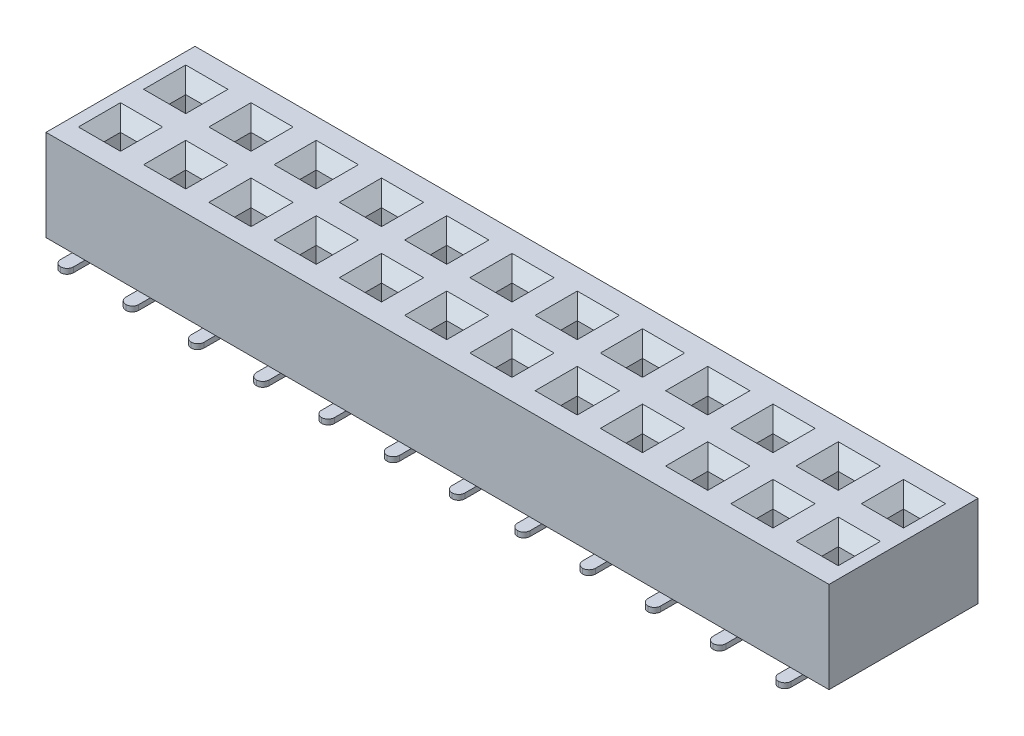
SolidWorks part; units mm, degrees
ref_plane "Ebene vorne" through (0, 0, 0) normal (0, 0, 1) x (1, 0, 0)
ref_plane "Ebene oben" through (0, 0, 0) normal (0, 1, 0) x (1, 0, 0)
ref_plane "Ebene rechts" through (0, 0, 0) normal (1, 0, 0) x (0, 0, -1)
sketch "Sketch1" plane through (0, 0, 0) normal (0, 1, 0) x (1, 0, 0)
  line L0 (0, 0) -> (20.1529, 0) construction
  line L1 (0, 2.9) -> (30.48, 2.9)
  line L2 (0, 2.9) -> (0, -2.9)
  line L3 (0, -2.9) -> (30.48, -2.9)
  line L4 (30.48, 2.9) -> (30.48, -2.9)
  dimension "D1" = 5.8
  dimension "D2" = 30.48
extrude "Boss-Extrude1" add sketch "Sketch1" along normal blind 3.55
sketch "Sketch2" plane through (0, 3.55, 0) normal (0, 1, 0) x (1, 0, 0)
  line L0 (0, 1.27) -> (30.48, 1.27) construction
  line L1 (0, 2.9) -> (0, -2.9) construction
  line L2 (30.48, -2.9) -> (30.48, 2.9) construction
  line L4 (0.95, 1.59) -> (1.59, 1.59)
  line L5 (0.95, 1.59) -> (0.95, 0.95)
  line L6 (0.95, 0.95) -> (1.59, 0.95)
  line L7 (1.59, 1.59) -> (1.59, 0.95)
  point P11 (1.27, 1.59)
  dimension "D1" = 0.64
  dimension "D2" = 1.27
  dimension "D3" = 1.27
extrude "Cut-Extrude1" cut sketch "Sketch2" against normal through all
chamfer "Chamfer1" distance 0.5 angle 45 4 edges at (1.27, 3.55, -0.95) (0.95, 3.55, -1.27) (1.27, 3.55, -1.59) (1.59, 3.55, -1.27)
pattern_linear "LPattern1" count 12 spacing 2.54 along (1, 0, 0) count 2 spacing 2.54 along (0, 0, 1) of "Cut-Extrude1", "Chamfer1"
sketch "Sketch3" plane through (0, 0, 0) normal (0, -1, 0) x (1, 0, 0)
  line L0 (1.27, 1.59) -> (1.27, -4.8164) construction
  line L1 (0.95, 1.59) -> (1.59, 1.59) construction
  line L2 (0, 0) -> (5.3011, 0) construction
  line L3 (1.02, 1.59) -> (1.52, 1.59)
  line L4 (1.02, 1.59) -> (1.02, 3.6)
  line L5 (1.02, 3.6) -> (1.52, 3.6)
  line L6 (1.52, 1.59) -> (1.52, 3.6)
  line L7 (1.52, -1.59) -> (1.52, -3.6)
  line L8 (1.02, -3.6) -> (1.52, -3.6)
  line L9 (1.02, -1.59) -> (1.02, -3.6)
  line L10 (1.02, -1.59) -> (1.52, -1.59)
  point P16 (1.3815, 1.1624)
  dimension "D1" = 7.2
  dimension "D2" = 0.5
extrude "Boss-Extrude2" add sketch "Sketch3" along normal blind 0.2
fillet "Fillet1" radius 0.25 4 edges at (1.02, -0.1, -3.6) (1.52, -0.1, -3.6) (1.02, -0.1, 3.6) (1.52, -0.1, 3.6)
pattern_linear "LPattern2" count 12 spacing 2.54 along (1, 0, 0) of "Fillet1", "Boss-Extrude2"
